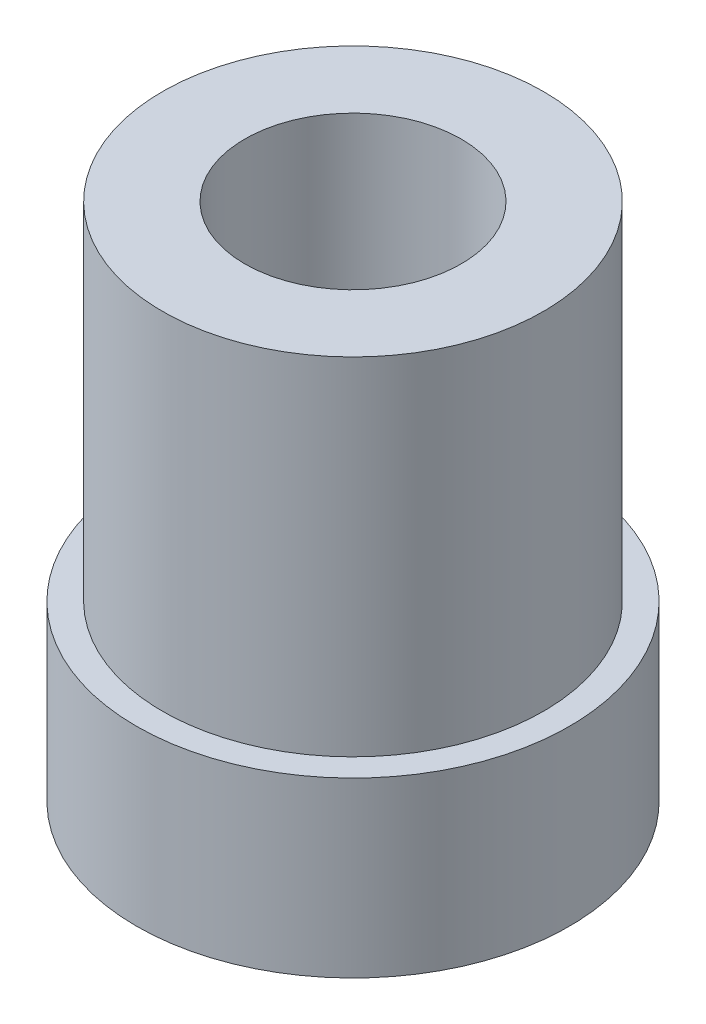
SolidWorks part; units mm, degrees
note: The reader was unsure of these and kept them because the rebuilt part matched: shared geometry of "Sketch2<3>".
material "6061-T6 (SS)"
ref_plane "Front Plane" through (0, 0, 0) normal (0, 0, 1) x (1, 0, 0)
ref_plane "Top Plane" through (0, 0, 0) normal (0, 1, 0) x (1, 0, 0)
ref_plane "Right Plane" through (0, 0, 0) normal (1, 0, 0) x (0, 0, -1)
sketch "Sketch1" plane through (0, 0, 0) normal (0, 1, 0) x (1, 0, 0)
  circle A0 centre (0, 0) radius 3.9688
  circle A1 centre (0, 0) radius 6.985
  circle A2 centre (0, 0) radius 7.9375
  dimension "D1" = 15.875
  dimension "D2" = 13.97
  dimension "D3" = 7.9375
extrude "Boss-Extrude1" add sketch "Sketch1" along normal blind 19.05 contours A1 A0
extrude "Boss-Extrude2" add sketch "Sketch2<3>" along normal blind 6.35 contours A2 A1
sketch "Sketch2<3>" plane through (0, 0, 0) normal (0, 1, 0) x (1, 0, 0) same geometry as "Sketch1"
thread "Thread1" [suppressed] start angle 0, offset 1, length 0, pitch 1.0583, diameter 6.9088
ref_plane "Plane1" through (3.4544, -1, 0) normal (0, 0, 1) x (1, 0, 0)
sketch "Thread Profile1" plane through (3.4544, -1, 0) normal (0, 0, 1) x (1, 0, 0)
  line L0 (0, 0) -> (0, 1.0583) construction
  line L1 (0, 0) -> (0.5728, 0.3307)
  line L2 (0.5728, 0.3307) -> (0.5728, 0.463)
  line L3 (0.5728, 0.463) -> (0, 0.7937)
  line L4 (0.5728, 0.3969) -> (0, 0.3969) construction
  line L11 (0, 0) -> (0, 0.7937)
  point P2 (0, 0)
  dimension "Pitch" = 1.0583
  dimension "Profile_Angle" = 60
  dimension "Profile_Land" = 0.1323
  dimension "Profile_Height" = 0.5728
